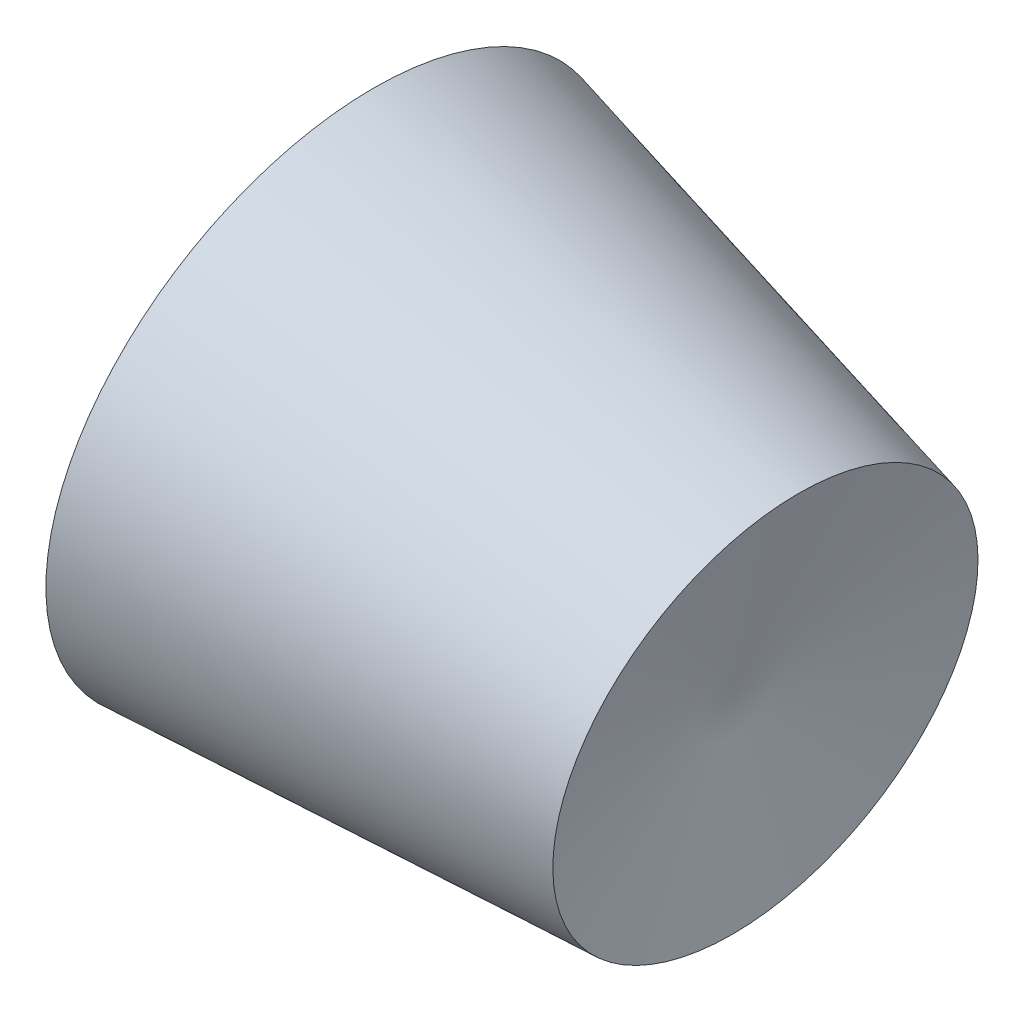
SolidWorks part; units mm, degrees
ref_plane "Front Plane" through (0, 0, 0) normal (0, 0, 1) x (1, 0, 0)
ref_plane "Top Plane" through (0, 0, 0) normal (0, 1, 0) x (1, 0, 0)
ref_plane "Right Plane" through (0, 0, 0) normal (1, 0, 0) x (0, 0, -1)
sketch "Sketch1" plane through (0, 0, 0) normal (0, 0, 1) x (1, 0, 0)
  line L0 (-60.6992, -21.0008) -> (-60.6992, 61.6476)
  line L1 (-60.6992, 61.6476) -> (40.9178, 74.9256)
  line L2 (40.9178, 74.9256) -> (124.3791, 61.6476)
  line L3 (124.3791, 61.6476) -> (124.3791, -26.4204)
  line L4 (124.3791, -26.4204) -> (-60.6992, -26.4204)
  line L5 (-60.6992, -26.4204) -> (-60.6992, -21.0008)
  line L7 (40.9178, 74.9256) -> (40.9178, -26.4204) construction
ref_axis "Axis1" through (40.9178, 74.9256, 0) along (0, -1, 0)
ref_plane "Plane1" through (0, 2.54, 0) normal (0, 1, 0) x (1, 0, 0)
sketch "Sketch2" plane through (0, 2.54, 0) normal (0, 1, 0) x (1, 0, 0)
  line L0 (40.9178, 0) -> (188.4655, 0) construction
  line L1 (211.2912, 0) -> (126.1045, 147.5478)
  line L2 (126.1045, 147.5478) -> (-44.269, 147.5478)
  line L3 (-44.269, 147.5478) -> (-129.4557, 0)
  line L4 (-129.4557, 0) -> (-44.269, -147.5478)
  line L5 (-44.269, -147.5478) -> (126.1045, -147.5478)
  line L6 (126.1045, -147.5478) -> (211.2912, 0)
  circle A0 centre (40.9178, 0) radius 147.5478 construction
revolve "Revolve2" add sketch "Sketch1" angle 360 about L2
